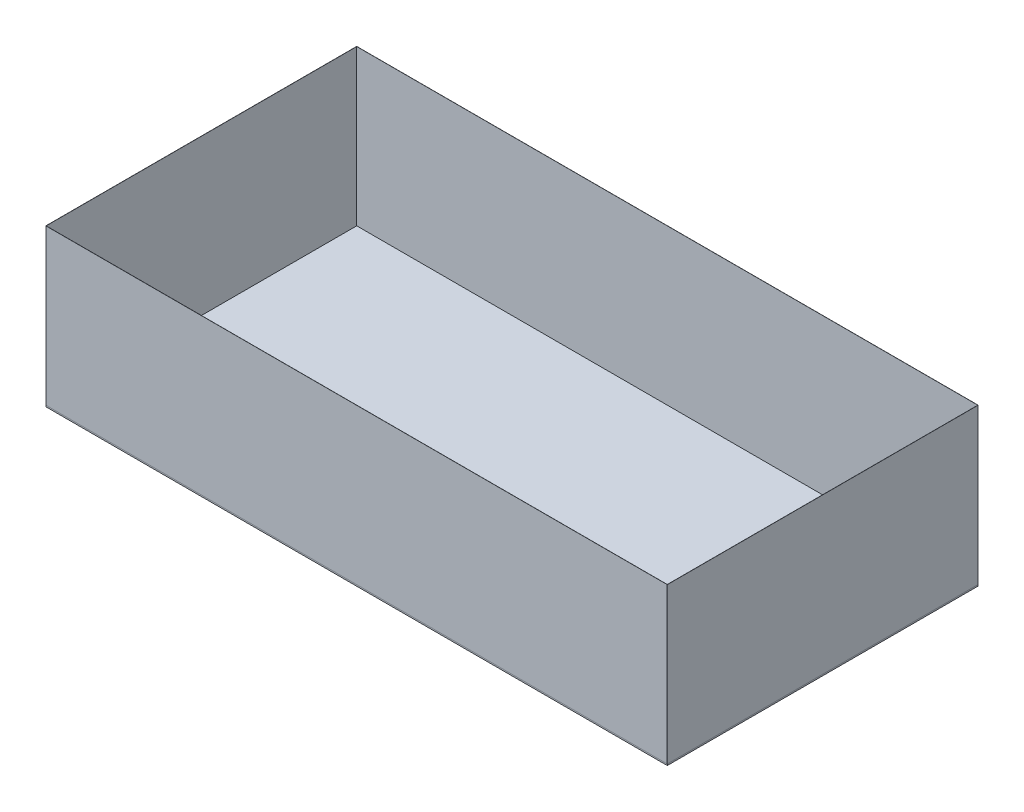
SolidWorks part; units mm, degrees
ref_plane "Front Plane" through (0, 0, 0) normal (0, 0, 1) x (1, 0, 0)
ref_plane "Top Plane" through (0, 0, 0) normal (0, 1, 0) x (1, 0, 0)
ref_plane "Right Plane" through (0, 0, 0) normal (1, 0, 0) x (0, 0, -1)
sketch "Sketch1" plane through (0, 0, 0) normal (0, 1, 0) x (1, 0, 0)
  line L1 (-75.5032, 22.1696) -> (26.0968, 22.1696)
  line L2 (-75.5032, 22.1696) -> (-75.5032, -28.6304)
  line L3 (-75.5032, -28.6304) -> (26.0968, -28.6304)
  line L4 (26.0968, 22.1696) -> (26.0968, -28.6304)
  dimension "Length_Floor" = 101.6
  dimension "Width_Floor" = 50.8
extrude "Floor" add sketch "Sketch1" along normal blind 0.254
sketch "Sketch2" plane through (0, 0.254, 0) normal (0, 1, 0) x (1, 0, 0)
  line L0 (26.0968, 22.1696) -> (-75.5032, 22.1696) construction
  line L1 (26.0968, 22.1696) -> (-75.5032, 22.1696)
extrude "Wall1" add sketch "Sketch2" along normal blind 25.4 separate body thin thin type one direction wall 0.0254
sketch "Sketch3" plane through (0, 0.254, 0) normal (0, 1, 0) x (1, 0, 0)
  line L0 (-75.5032, 22.1696) -> (-75.5032, -28.6304) construction
  line L1 (-75.5032, 22.1696) -> (-75.5032, -28.6304)
extrude "Wall2" add sketch "Sketch3" along normal blind 25.4 separate body thin thin type one direction wall 0.0254
sketch "Sketch4" plane through (0, 0.254, 0) normal (0, 1, 0) x (1, 0, 0)
  line L0 (-75.5032, -28.6304) -> (26.0968, -28.6304) construction
  line L1 (-75.5032, -28.6304) -> (26.0968, -28.6304)
extrude "Wall3" add sketch "Sketch4" along normal blind 25.4 separate body thin thin type one direction wall 0.0254
sketch "Sketch5" plane through (0, 0.254, 0) normal (0, 1, 0) x (1, 0, 0)
  line L0 (26.0968, -28.6304) -> (26.0968, 22.1696) construction
  line L1 (26.0968, -28.6304) -> (26.0968, 22.1696)
extrude "Wall4" add sketch "Sketch5" along normal blind 25.4 separate body thin thin type one direction wall 0.0254
